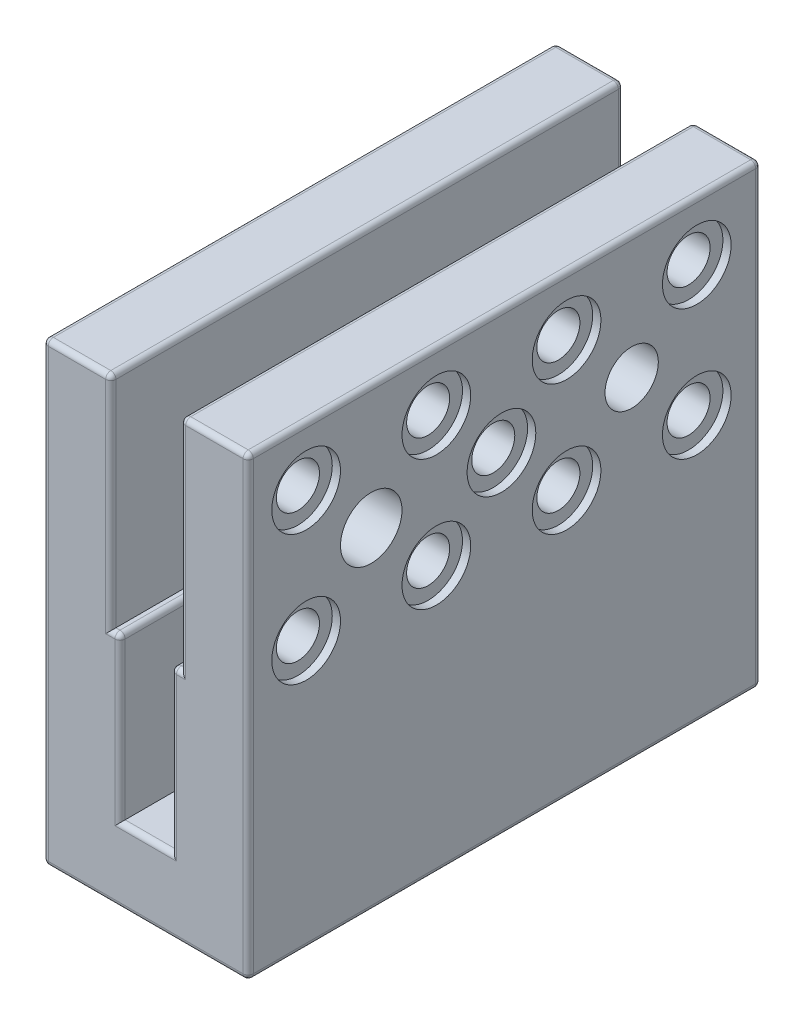
SolidWorks part; units mm, degrees
ref_plane "Front Plane" through (0, 0, 0) normal (0, 0, 1) x (1, 0, 0)
ref_plane "Top Plane" through (0, 0, 0) normal (0, 1, 0) x (1, 0, 0)
ref_plane "Right Plane" through (0, 0, 0) normal (1, 0, 0) x (0, 0, -1)
sketch "Sketch2" plane through (0, 0, 0) normal (0, 1, 0) x (1, 0, 0)
  line L1 (-10, 25) -> (10, 25)
  line L2 (-10, 25) -> (-10, -25)
  line L3 (-10, -25) -> (10, -25)
  line L4 (10, 25) -> (10, -25)
  line L5 (-10, 25) -> (10, -25) construction
  line L6 (-10, -25) -> (10, 25) construction
  point P1 (0, 0)
  dimension "D1" = 20
  dimension "D2" = 50
extrude "Boss-Extrude1" add sketch "Sketch2" along normal blind 44.5
sketch "Sketch3" plane through (0, 0, 25) normal (0, 0, 1) x (1, 0, 0)
  line L0 (-10, 44.5) -> (10, 44.5) construction
  line L1 (-3.4, 44.5) -> (3.4, 44.5)
  line L2 (-3.4, 44.5) -> (-3.4, 23.02)
  line L3 (-3.4, 23.02) -> (3.4, 23.02)
  line L4 (3.4, 44.5) -> (3.4, 23.02)
  line L7 (-2.5, 7.25) -> (2.5, 7.25)
  line L8 (-2.5, 7.25) -> (-2.5, 23.02)
  line L9 (-2.5, 23.02) -> (2.5, 23.02)
  line L10 (2.5, 7.25) -> (2.5, 23.02)
  point P8 (0, 23.02)
  point P12 (0, 23.02)
  dimension "D1" = 6.8
  dimension "D2" = 21.48
  dimension "D3" = 5
  dimension "D4" = 15.77
extrude "Cut-Extrude3" cut sketch "Sketch3" against normal through all contours L10 L9 L8 L7 | L2 L3 L4 L1
sketch "Sketch4" plane through (10, 0, 0) normal (1, 0, 0) x (0, 0, -1)
  line L0 (-25, 0) -> (25, 0) construction
  line L1 (-25, 44.5) -> (-25, 23.02) construction
  line L2 (-13, 32.41) -> (21.4534, 32.41) construction
  line L3 (-19.35, 38.76) -> (21.4534, 38.76) construction
  circle A0 centre (-13, 32.41) radius 3
  circle A7 centre (-0.3, 32.41) radius 2.1
  circle A8 centre (12.4, 32.41) radius 2.6
  circle A9 centre (-19.35, 38.76) radius 2.1
  circle A10 centre (-6.65, 38.76) radius 2.1
  circle A11 centre (6.05, 38.76) radius 2.1
  circle A12 centre (18.75, 38.76) radius 2.1
  circle A13 centre (18.75, 26.06) radius 2.1
  circle A14 centre (6.05, 26.06) radius 2.1
  circle A15 centre (-6.65, 26.06) radius 2.1
  circle A16 centre (-19.35, 26.06) radius 2.1
  dimension "D3" = 6
  dimension "D6" = 4.2
  dimension "D7" = 5.2
  dimension "D10" = 4.2
  dimension "D11" = 4.2
  dimension "D12" = 4.2
  dimension "D16" = 4.2
  dimension "D1" = 32.41
  dimension "D2" = 12
  dimension "D4" = 12.7
  dimension "D5" = 12.7
  dimension "D8" = 6.35
  dimension "D9" = 6.35
  dimension "D13" = 12.7
  dimension "D14" = 12.7
  dimension "D15" = 12.7
extrude "Cut-Extrude4" cut sketch "Sketch4" against normal through all contours A8 | A0
extrude "Cut-Extrude5" cut sketch "Sketch4<3>" against normal up to next contours A10 | A9 | A13 | A12 | A14 | A11 | A15 | A16 | A7
sketch "Sketch4<3>" plane through (10, 0, 0) normal (1, 0, 0) x (0, 0, -1) same geometry as "Sketch4"
sketch "Sketch5" plane through (-10, 0, 0) normal (-1, 0, 0) x (0, 0, 1)
  circle A0 centre (13, 32.41) radius 2.6
  circle A1 centre (13, 32.41) radius 3
  dimension "D1" = 5.2
  dimension "D2" = 6
extrude "Boss-Extrude2" add sketch "Sketch5" against normal blind 6.6
sketch "Sketch6" plane through (3.4, 0, 0) normal (-1, 0, 0) x (0, 0, 1)
  circle A0 centre (-18.75, 26.06) radius 3.1
  circle A1 centre (-18.75, 38.76) radius 3.1
  circle A2 centre (-6.05, 38.76) radius 3.1
  circle A3 centre (6.65, 38.76) radius 3.1
  circle A4 centre (0.3, 32.41) radius 3.1
  circle A5 centre (-6.05, 26.06) radius 3.1
  circle A6 centre (6.65, 26.06) radius 3.1
  circle A7 centre (19.35, 26.06) radius 3.1
  circle A8 centre (19.35, 38.76) radius 3.1
  dimension "D1" = 6.2
extrude "Cut-Extrude6" cut sketch "Sketch6" against normal blind 1.23
sketch "Sketch7" plane through (-10, 0, 0) normal (-1, 0, 0) x (0, 0, 1)
  line L0 (-25, 0) -> (25, 0) construction
  line L1 (-18.6, 3.48) -> (-14, 3.48)
  line L2 (-18.6, 3.48) -> (-18.6, 23.58)
  line L3 (-18.6, 23.58) -> (-14, 23.58)
  line L4 (-14, 3.48) -> (-14, 23.58)
  line L5 (-25, 44.5) -> (-25, 0) construction
  dimension "D1" = 3.48
  dimension "D2" = 20.1
  dimension "D3" = 4.6
  dimension "D4" = 6.4
extrude "Cut-Extrude7" cut sketch "Sketch7" against normal blind 3.25
fillet "Fillet1" radius 0.5 32 edges at (-10, 0, 0) (10, 0, 0) (-10, 22.25, -25) (0, 0, -25) (10, 22.25, -25) (3.4, 33.76, -25) (2.95, 23.02, -25) (2.5, 15.135, -25) (0, 7.25, -25) (-2.5, 15.135, -25) (-2.95, 23.02, -25) (-3.4, 33.76, -25) (-2.5, 15.135, 25) (0, 7.25, 25) (2.5, 15.135, 25) (2.95, 23.02, 25) (3.4, 33.76, 25) (10, 22.25, 25) (0, 0, 25) (-10, 22.25, 25) (-3.4, 33.76, 25) (-2.95, 23.02, 25) (10, 44.5, 0) (6.7, 44.5, 25) (3.4, 44.5, 0) (6.7, 44.5, -25) (-6.7, 44.5, 25) (-10, 44.5, 0) (-6.7, 44.5, -25) (-3.4, 44.5, 0) (2.5, 23.02, 0) (-2.5, 23.02, 0)
sketch "Sketch8" plane through (10, 0, 0) normal (1, 0, 0) x (0, 0, -1)
  circle A0 centre (-19.35, 38.76) radius 3.35
  circle A1 centre (-6.65, 38.76) radius 3.35
  circle A2 centre (6.05, 38.76) radius 3.35
  circle A3 centre (18.75, 38.76) radius 3.35
  circle A4 centre (-0.3, 32.41) radius 3.35
  circle A5 centre (-19.35, 26.06) radius 3.35
  circle A6 centre (-6.65, 26.06) radius 3.35
  circle A7 centre (6.05, 26.06) radius 3.35
  circle A8 centre (18.75, 26.06) radius 3.35
  dimension "D1" = 6.7
extrude "Cut-Extrude8" cut sketch "Sketch8" against normal blind 0.8
